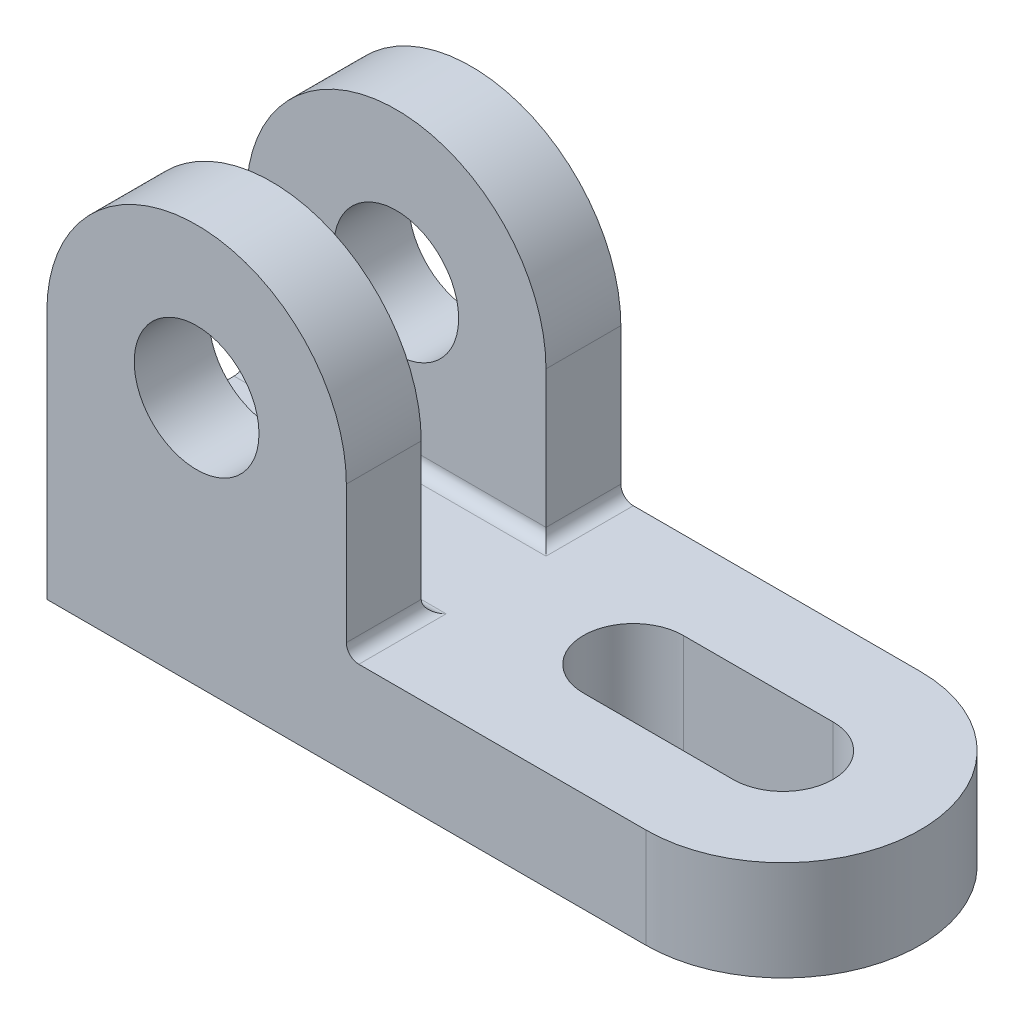
SolidWorks part; units mm, degrees
ref_plane "Front Plane" through (0, 0, 0) normal (0, 0, 1) x (1, 0, 0)
ref_plane "Top Plane" through (0, 0, 0) normal (0, 1, 0) x (1, 0, 0)
ref_plane "Right Plane" through (0, 0, 0) normal (1, 0, 0) x (0, 0, -1)
sketch "Sketch1" plane through (0, 0, 0) normal (0, 1, 0) x (1, 0, 0)
  line L1 (-43.7982, 94.9068) -> (200.0418, 94.9068)
  line L2 (-43.7982, 94.9068) -> (-43.7982, -16.8532)
  line L3 (-43.7982, -16.8532) -> (200.0418, -16.8532)
  arc A0 (200.0418, 94.9068) -> (200.0418, -16.8532) centre (200.0418, 39.0268) cw
  dimension "D1" = 111.76
  dimension "D2" = 243.84
extrude "Boss-Extrude1" add sketch "Sketch1" along normal blind 40.64
sketch "Sketch2" plane through (0, 40.64, 0) normal (0, 1, 0) x (1, 0, 0)
  line L0 (200.0418, 94.9068) -> (200.0418, -16.8532) construction
  line L1 (200.0418, 39.0268) -> (139.0818, 39.0268) construction
  line L2 (200.0418, 59.3468) -> (139.0818, 59.3468)
  line L3 (200.0418, 18.7068) -> (139.0818, 18.7068)
  line L4 (-43.7982, 39.0268) -> (83.2018, 39.0268) construction
  line L5 (-43.7982, 94.9068) -> (-43.7982, -16.8532) construction
  line L6 (83.2018, 39.0268) -> (83.2018, -16.8532) construction
  line L7 (-43.7982, -16.8532) -> (200.0418, -16.8532) construction
  line L8 (83.2018, 39.0268) -> (83.2018, 94.9068) construction
  line L9 (200.0418, 94.9068) -> (-43.7982, 94.9068) construction
  line L10 (83.2018, 18.7068) -> (-43.7982, 18.7068)
  line L11 (83.2018, 18.7068) -> (83.2018, -16.8532)
  line L12 (83.2018, 59.3468) -> (83.2018, 94.9068)
  line L13 (83.2018, 59.3468) -> (-43.7982, 59.3468)
  line L14 (78.1218, 13.6268) -> (78.1218, -16.8532)
  line L15 (78.1218, 13.6268) -> (-43.7982, 13.6268)
  line L16 (78.1218, 64.4268) -> (78.1218, 94.9068)
  line L17 (78.1218, 64.4268) -> (-43.7982, 64.4268)
  line L18 (78.1218, 94.9068) -> (-43.7982, 94.9068)
  line L19 (-43.7982, 94.9068) -> (-43.7982, 64.4268)
  line L20 (-43.7982, 13.6268) -> (-43.7982, -16.8532)
  line L21 (-43.7982, -16.8532) -> (78.1218, -16.8532)
  line L22 (83.2018, -16.8532) -> (78.1218, -16.8532)
  line L23 (-43.7982, 18.7068) -> (-43.7982, 13.6268)
  line L24 (-43.7982, 59.3468) -> (-43.7982, 64.4268)
  line L25 (78.1218, 94.9068) -> (83.2018, 94.9068)
  arc A2 (200.0418, 59.3468) -> (200.0418, 18.7068) centre (200.0418, 39.0268) cw
  arc A3 (139.0818, 59.3468) -> (139.0818, 18.7068) centre (139.0818, 39.0268) ccw
  line M14 (-43.7982, 94.9068) -> (-43.7982, -16.8532)
  line M15 (-43.7982, -16.8532) -> (200.0418, -16.8532)
  line M17 (200.0418, 94.9068) -> (-43.7982, 94.9068)
  dimension "D1" = 40.64
  dimension "D3" = 127
  dimension "D2" = 60.96
  dimension "D4" = 35.56
  dimension "D5" = 5.08
extrude "Boss-Extrude3" add sketch "Sketch2" along normal blind 121.92 contours L14 L15 M14 M15 | L17 L16 M17 M14 region at (17.1618, 40.64, 1.6132) region at (17.1618, 40.64, -79.6668)
extrude "Cut-Extrude1" cut sketch "Sketch2<6>" against normal blind 40.64 contours L3 A3 L2 A2
sketch "Sketch2<6>" plane through (0, 40.64, 0) normal (0, 1, 0) x (1, 0, 0) same geometry as "Sketch2"
sketch "Sketch5" plane through (0, 0, 16.8532) normal (0, 0, 1) x (1, 0, 0)
  line L0 (-43.7982, 101.6) -> (-43.7982, 162.56)
  line L3 (-43.7982, 0) -> (-43.7982, 101.6)
  line L4 (-43.7982, 162.56) -> (-43.7982, 0) construction
  line L5 (78.1218, 162.56) -> (78.1218, 40.64) construction
  line L6 (-43.7982, 101.6) -> (78.1218, 101.6) construction
  line L7 (-43.7982, 162.56) -> (17.1618, 162.56)
  line L8 (78.1218, 101.6) -> (78.1218, 162.56)
  line L9 (78.1218, 162.56) -> (17.1618, 162.56)
  arc A0 (-43.7982, 101.6) -> (78.1218, 101.6) centre (17.1618, 101.6) cw
  circle A1 centre (17.1618, 101.6) radius 25.4
  line M5 (78.1218, 40.64) -> (78.1218, 162.56)
  line M6 (78.1218, 162.56) -> (-43.7982, 162.56)
  line M7 (-43.7982, 162.56) -> (-43.7982, 0)
  dimension "D1" = 101.6
  dimension "D2" = 50.8
extrude "Cut-Extrude3" cut sketch "Sketch5" against normal blind 111.76 contours A0 M6 M5 | A0 M7 M6 region at (64.5053, 148.9435, 16.8532) region at (-30.1817, 148.9435, 16.8532)
extrude "Cut-Extrude4" cut sketch "Sketch5<5>" against normal blind 111.76 contours A1
sketch "Sketch5<5>" plane through (0, 0, 16.8532) normal (0, 0, 1) x (1, 0, 0) same geometry as "Sketch5"
fillet "Fillet1" radius 5.08 4 edges at (78.1218, 40.64, 1.6132) (17.1618, 40.64, -13.6268) (17.1618, 40.64, -64.4268) (78.1218, 40.64, -79.6668)
